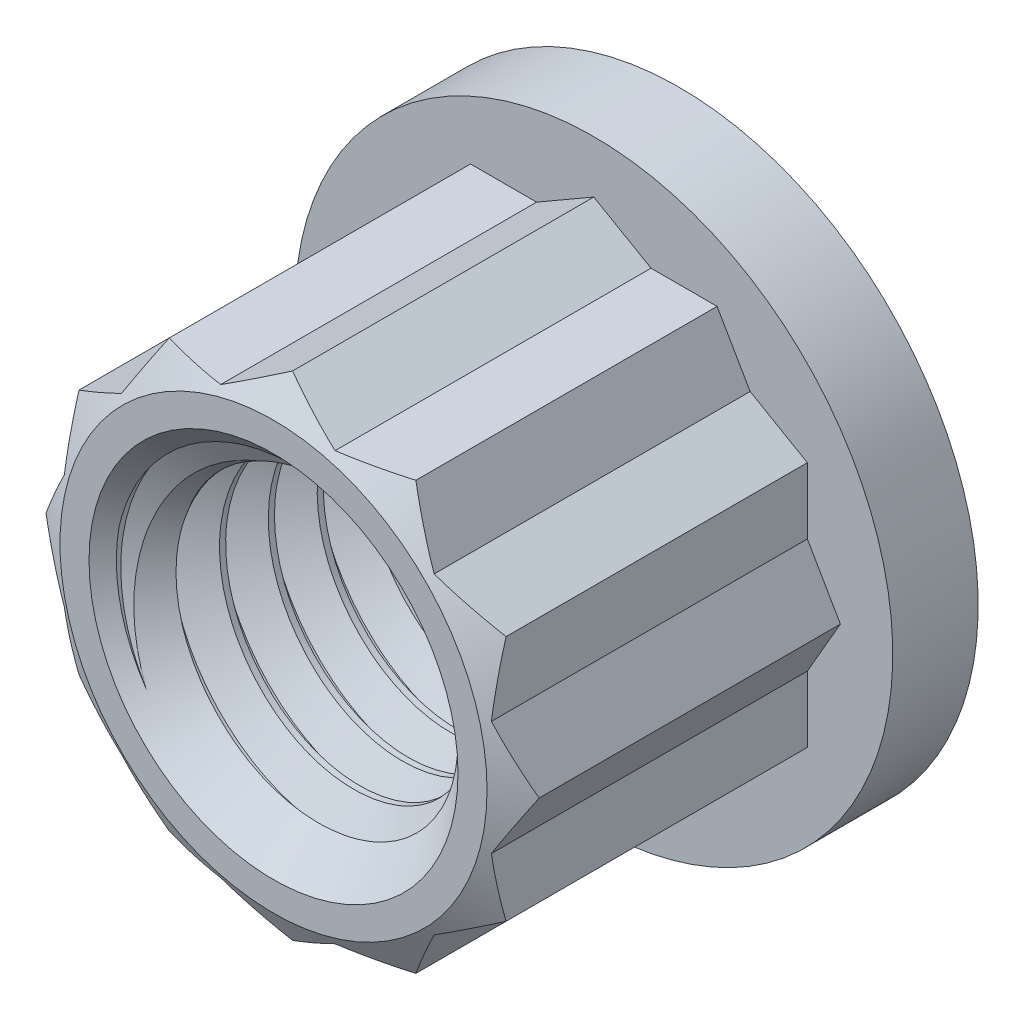
SolidWorks part; units mm, degrees
material "Plain Carbon Steel"
ref_plane "Front Plane" through (0, 0, 0) normal (0, 0, 1) x (1, 0, 0)
ref_plane "Top Plane" through (0, 0, 0) normal (0, 1, 0) x (1, 0, 0)
ref_plane "Right Plane" through (0, 0, 0) normal (1, 0, 0) x (0, 0, -1)
sketch "Sketch1" plane through (0, 0, 0) normal (0, 0, 1) x (1, 0, 0)
  line L1 (0, 4.5827) -> (-3.9688, 2.2914)
  line L2 (-3.9688, 2.2914) -> (-3.9688, -2.2914)
  line L3 (-3.9688, -2.2914) -> (0, -4.5827)
  line L4 (0, -4.5827) -> (3.9688, -2.2914)
  line L5 (3.9688, -2.2914) -> (3.9688, 2.2914)
  line L6 (3.9688, 2.2914) -> (0, 4.5827)
  circle A0 centre (0, 0) radius 3.9688 construction
  dimension "Hex" = 7.9375
extrude "Extrude1" add sketch "Sketch1" against normal blind 7.5406
sketch "Sketch14" plane through (0, 0, 0) normal (0, 0, 1) x (1, 0, 0)
  line L1 (-2.2914, 3.9688) -> (-4.5827, 0)
  line L2 (-4.5827, 0) -> (-2.2914, -3.9688)
  line L3 (-2.2914, -3.9688) -> (2.2914, -3.9688)
  line L4 (2.2914, -3.9688) -> (4.5827, 0)
  line L5 (4.5827, 0) -> (2.2914, 3.9688)
  line L6 (2.2914, 3.9688) -> (-2.2914, 3.9688)
  circle A0 centre (0, 0) radius 3.9688 construction
  circle A1 centre (0, 0) radius 3.9688 construction
extrude "Extrude4" add sketch "Sketch14" against normal up to surface (7.5406 mm away) up to face at (0, 0, -7.5406)
sketch "Sketch13" plane through (0, 0, -7.5406) normal (0, 0, -1) x (-1, 0, 0)
  circle A0 centre (0, 0) radius 5.5562
  dimension "Flange od" = 11.1125
extrude "Extrude3" add sketch "Sketch13" against normal blind 1.5875
sketch "Sketch2" plane through (0, 0, 0) normal (0, 0, 1) x (1, 0, 0)
  circle A0 centre (0, 0) radius 3.9688 construction
  circle A1 centre (0, 0) radius 3.9688
extrude "Cut-Extrude1" cut sketch "Sketch2" against normal through all draft 60 flip side to cut
sketch "Sketch4" plane through (0, 0, 0) normal (0, 0, 1) x (1, 0, 0)
  circle A0 centre (0, 0) radius 3.175
  dimension "Thread Dia" = 6.35
extrude "Cut-Extrude3" cut sketch "Sketch4" against normal through all
sketch "Sketch7" plane through (0, 0, 0) normal (0, 0, 1) x (1, 0, 0)
  circle A4 centre (0, 0) radius 3.429
  circle A5 centre (0, 0) radius 3.429
  dimension "D1" = 0.254
sketch "Sketch8" plane through (0, 0, -7.5406) normal (0, 0, -1) x (-1, 0, 0)
  circle A1 centre (0, 0) radius 3.429
  circle A2 centre (0, 0) radius 3.429 construction
sketch "Sketch5" plane through (0, 0, 0) normal (0, 0, 1) x (1, 0, 0)
  circle A0 centre (0, 0) radius 3.175 construction
  circle A1 centre (0, 0) radius 3.175
curve "Helix/Spiral1" pitch 0.9071 height 8.4478 turns 9.3125 parameters "pitch"=0.9071
sketch "Sketch9" plane through (0, 0, 0) normal (1, 0, 0) x (0, 0, -1)
  line L0 (-0.4536, 3.175) -> (-0.3402, 3.175)
  line L1 (-0.3402, 3.175) -> (0, 2.5858)
  line L2 (-0.4536, 3.175) -> (-0.7938, 2.5858)
  line L3 (-0.7938, 2.5858) -> (0, 2.5858)
  line L4 (-0.3969, 3.175) -> (-0.3969, 2.5858) construction
  line L5 (-0.6237, 2.8804) -> (-0.1701, 2.8804) construction
  line L7 (0, 2.5858) -> (0, 3.175) construction
  line L8 (0, 3.175) -> (0, -3.175) construction
  dimension "D1" = 0.1134
  dimension "D2" = 0.4536
  dimension "D3" = 60
sketch "Sketch12" plane through (0, 0, 0) normal (0, 0, 1) x (1, 0, 0)
  circle A0 centre (0, 0) radius 2.5858
  circle A1 centre (0, 0) radius 3.175 construction
  circle A2 centre (0, 0) radius 3.175
extrude "Extrude2" add sketch "Sketch12" against normal up to surface (7.5406 mm away) up to face at (3.175, 0, -7.5406)
sweep "Cut-Sweep1" cut profiles "Sketch9" path "Helix/Spiral1"
extrude "Cut-Extrude6" cut sketch "Sketch7" against normal through all draft 45
extrude "Cut-Extrude7" cut sketch "Sketch8" against normal through all draft 45
equation "\"D2@Sketch9\" = \"pitch@Helix/Spiral1\"*.5"
equation "\"D3@Helix/Spiral1\" = \"pitch@Helix/Spiral1\"+\"Height@Extrude1\""
equation "\"D1@Sketch9\" = \"pitch@Helix/Spiral1\"*.125"
